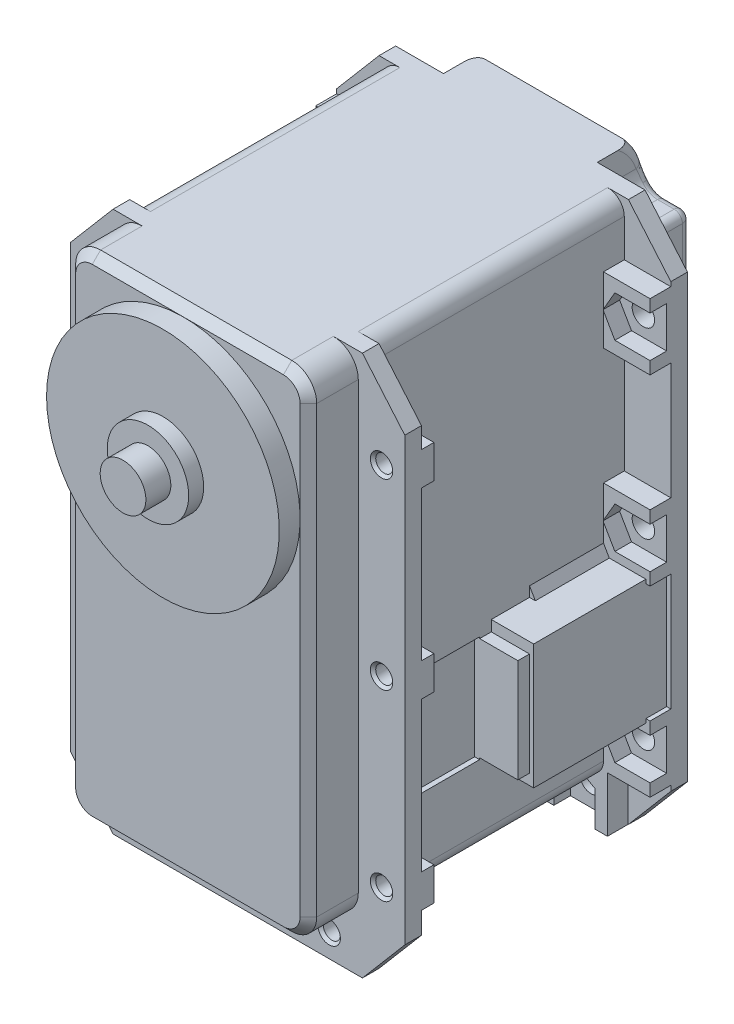
SolidWorks part; units mm, degrees
material "Custom Plastic"
ref_plane "Front Plane" through (0, 0, 0) normal (0, 0, 1) x (1, 0, 0)
ref_plane "Top Plane" through (0, 0, 0) normal (0, 1, 0) x (1, 0, 0)
ref_plane "Right Plane" through (0, 0, 0) normal (1, 0, 0) x (0, 0, -1)
ref_plane "Plane1" through (9.25, 0, 0) normal (1, 0, 0) x (0, 0, -1)
sketch "Sketch1" plane through (9.25, 0, 0) normal (1, 0, 0) x (0, 0, -1)
  line L0 (21, 14.5) -> (21, 9.5)
  line L1 (21, 9.5) -> (23, 9.5)
  arc A0 (23, 9.5) -> (21, 14.5) centre (15.75, 9.5) ccw
extrude "Boss-Extrude1" add sketch "Sketch1" against normal blind 18.5
ref_plane "Plane2" through (0, 9.5, 0) normal (0, -1, 0) x (1, 0, 0)
sketch "Sketch2" plane through (0, 9.5, 0) normal (0, -1, 0) x (1, 0, 0)
  line L0 (-15.8711, -21) -> (-15.8711, -23)
  line L1 (-15.8711, -23) -> (-9.25, -23)
  line L2 (-9.25, -23) -> (-9.25, -21)
  line L3 (-9.25, -21) -> (-15.8711, -21)
extrude "Boss-Extrude2" add sketch "Sketch2" against normal blind 5
sketch "Sketch3" plane through (0, 9.5, 0) normal (0, -1, 0) x (1, 0, 0)
  line L0 (9.25, -21) -> (9.25, -23)
  line L1 (9.25, -23) -> (20.1, -23)
  line L2 (20.1, -23) -> (20.1, -21)
  line L3 (20.1, -21) -> (9.25, -21)
extrude "Boss-Extrude3" add sketch "Sketch3" against normal blind 5
sketch "Sketch4" plane through (0, 9.5, 0) normal (0, -1, 0) x (1, 0, 0)
  line L0 (20.1, -21) -> (20.1, -23)
  line L1 (20.1, -23) -> (-15.8711, -23)
  line L2 (-15.8711, -23) -> (-15.8711, -21)
  line L3 (-15.8711, -21) -> (20.1, -21)
extrude "Boss-Extrude4" add sketch "Sketch4" along normal blind 60.1
sketch "Sketch5" plane through (0, 0, -21) normal (0, 0, 1) x (1, 0, 0)
  line L0 (-15.8711, -50.6) -> (-15.8711, 14.5)
  line L1 (-15.8711, 14.5) -> (20.1, 14.5)
  line L2 (20.1, 14.5) -> (20.1, -50.6)
  line L3 (20.1, -50.6) -> (-15.8711, -50.6)
extrude "Boss-Extrude5" add sketch "Sketch5" along normal blind 6.5
sketch "Sketch6" plane through (0, 0, -23) normal (0, 0, -1) x (-1, 0, 0)
  line L0 (15.8711, -50.6) -> (15.8711, 14.5)
  line L1 (15.8711, 14.5) -> (9.25, 14.5)
  line L2 (9.25, 14.5) -> (9.25, -45)
  line L3 (9.25, -45) -> (-9.25, -45)
  line L4 (-9.25, -45) -> (-9.25, 14.5)
  line L5 (-9.25, 14.5) -> (-20.1, 14.5)
  line L6 (-20.1, 14.5) -> (-20.1, -50.6)
  line L7 (-20.1, -50.6) -> (15.8711, -50.6)
extrude "Cut-Extrude1" cut sketch "Sketch6" against normal blind 2
sketch "Sketch7" plane through (0, 0, -14.5) normal (0, 0, 1) x (1, 0, 0)
  line L0 (-15.8711, -20.475) -> (-14.5, -18.1003)
  line L1 (-14.5, -18.1003) -> (-14.5, -17.8997)
  line L2 (-14.5, -17.8997) -> (-15.8711, -15.525)
  line L3 (-15.8711, -15.525) -> (-15.8711, 1.525)
  line L4 (-15.8711, 1.525) -> (-14.5, 3.8997)
  line L5 (-14.5, 3.8997) -> (-14.5, 4.1003)
  line L6 (-14.5, 4.1003) -> (-15.8711, 6.475)
  line L7 (-15.8711, 6.475) -> (-15.8711, 14.5)
  line L8 (-15.8711, 14.5) -> (20.1, 14.5)
  line L9 (20.1, 14.5) -> (20.1, -50.6)
  line L10 (20.1, -50.6) -> (-15.8711, -50.6)
  line L11 (-15.8711, -50.6) -> (-15.8711, -42.475)
  line L12 (-15.8711, -42.475) -> (-14.5, -40.1003)
  line L13 (-14.5, -40.1003) -> (-14.5, -39.8997)
  line L14 (-14.5, -39.8997) -> (-15.8711, -37.525)
  line L15 (-15.8711, -37.525) -> (-15.8711, -20.475)
extrude "Boss-Extrude6" add sketch "Sketch7" along normal blind 2
sketch "Sketch8" plane through (0, 0, -21) normal (0, 0, -1) x (-1, 0, 0)
  line L0 (15.8711, -50.6) -> (15.8711, 14.5)
  line L1 (15.8711, 14.5) -> (9.25, 14.5)
  line L2 (9.25, 14.5) -> (9.25, -45)
  line L3 (9.25, -45) -> (-9.25, -45)
  line L4 (-9.25, -45) -> (-9.25, 14.5)
  line L5 (-9.25, 14.5) -> (-20.1, 14.5)
  line L6 (-20.1, 14.5) -> (-20.1, -50.6)
  line L7 (-20.1, -50.6) -> (15.8711, -50.6)
extrude "Cut-Extrude2" cut sketch "Sketch8" against normal blind 4
sketch "Sketch9" plane through (0, 0, -12.5) normal (0, 0, 1) x (1, 0, 0)
  line L0 (20.1, 14.5) -> (20.1, -50.6)
  line L1 (20.1, -50.6) -> (-15.8711, -50.6)
  line L2 (-15.8711, -50.6) -> (-15.8711, -42.475)
  line L3 (-15.8711, -42.475) -> (-14.5, -40.1003)
  line L4 (-14.5, -40.1003) -> (-14.5, 14.5)
  line L5 (-14.5, 14.5) -> (20.1, 14.5)
extrude "Boss-Extrude7" add sketch "Sketch9" along normal blind 29.5
sketch "Sketch10" plane through (0, 0, 17) normal (0, 0, 1) x (1, 0, 0)
  line L0 (14.5, 14.5) -> (14.5, -45)
  line L1 (14.5, -45) -> (-14.5, -45)
  line L2 (-14.5, -45) -> (-14.5, -40.1003)
  line L3 (-14.5, -40.1003) -> (-15.8711, -42.475)
  line L4 (-15.8711, -42.475) -> (-15.8711, -50.6)
  line L5 (-15.8711, -50.6) -> (20.1, -50.6)
  line L6 (20.1, -50.6) -> (20.1, 14.5)
  line L7 (20.1, 14.5) -> (14.5, 14.5)
extrude "Cut-Extrude3" cut sketch "Sketch10" against normal blind 29.5
sketch "Sketch11" plane through (0, 0, -12.5) normal (0, 0, 1) x (1, 0, 0)
  line L0 (-13.475, -46.3711) -> (-13.475, -50.6)
  line L1 (-13.475, -50.6) -> (-8.525, -50.6)
  line L2 (-8.525, -50.6) -> (-8.525, -46.3711)
  line L3 (-8.525, -46.3711) -> (-11, -44.9421)
  line L4 (-11, -44.9421) -> (-13.475, -46.3711)
extrude "Cut-Extrude4" cut sketch "Sketch11" against normal blind 2
sketch "Sketch12" plane through (0, 0, -12.5) normal (0, 0, 1) x (1, 0, 0)
  line L0 (8.525, -46.3711) -> (8.525, -50.6)
  line L1 (8.525, -50.6) -> (13.475, -50.6)
  line L2 (13.475, -50.6) -> (13.475, -46.3711)
  line L3 (13.475, -46.3711) -> (11, -44.9421)
  line L4 (11, -44.9421) -> (8.525, -46.3711)
extrude "Cut-Extrude5" cut sketch "Sketch12" against normal blind 2
sketch "Sketch13" plane through (0, 0, -12.5) normal (0, 0, 1) x (1, 0, 0)
  line L0 (15.8711, -42.475) -> (20.1, -42.475)
  line L1 (20.1, -42.475) -> (20.1, -37.525)
  line L2 (20.1, -37.525) -> (15.8711, -37.525)
  line L3 (15.8711, -37.525) -> (14.4421, -40)
  line L4 (14.4421, -40) -> (15.8711, -42.475)
extrude "Cut-Extrude6" cut sketch "Sketch13" against normal blind 2
sketch3d "3DSketch1"
  point P0 (0.3206, -15.6432, -2.4982)
  point P1 (0.3206, 84.3568, -2.4982)
ref_axis "Axis1" through (0.3206, -15.6432, -2.4982) along (0, 1, 0)
pattern_linear "LPattern1" count 3 spacing 22 along (0, 1, 0) of "Cut-Extrude6"
ref_plane "Plane3" through (0, 0, -14.5) normal (0, 0, -1) x (-1, 0, 0)
sketch "Sketch14" plane through (0, 0, -14.5) normal (0, 0, -1) x (-1, 0, 0)
  line L0 (14.4421, -40) -> (14.5, -40.1003)
  line L1 (14.5, -40.1003) -> (14.5, -39.8997)
  line L2 (14.5, -39.8997) -> (14.4421, -40)
extrude "Cut-Extrude7" cut sketch "Sketch14" against normal blind 2
sketch3d "3DSketch2"
  point P0 (0.2957, -15.6557, -2.4823)
  point P1 (0.2957, 84.3443, -2.4823)
ref_axis "Axis2" through (0.2957, -15.6557, -2.4823) along (0, 1, 0)
pattern_linear "LPattern2" count 3 spacing 22 along (0, 1, 0) of "Cut-Extrude7"
sketch "Sketch15" plane through (-15.8711, 0, 0) normal (-1, 0, 0) x (0, 0, 1)
  line L0 (-12.5, 14.5) -> (-12.5, 6.475)
  line L1 (-12.5, 6.475) -> (-14.5, 6.475)
  line L2 (-14.5, 6.475) -> (-14.5, 1.525)
  line L3 (-14.5, 1.525) -> (-12.5, 1.525)
  line L4 (-12.5, 1.525) -> (-12.5, -15.525)
  line L5 (-12.5, -15.525) -> (-14.5, -15.525)
  line L6 (-14.5, -15.525) -> (-14.5, -20.475)
  line L7 (-14.5, -20.475) -> (-12.5, -20.475)
  line L8 (-12.5, -20.475) -> (-12.5, -37.525)
  line L9 (-12.5, -37.525) -> (-14.5, -37.525)
  line L10 (-14.5, -37.525) -> (-14.5, -42.475)
  line L11 (-14.5, -42.475) -> (-12.5, -42.475)
  line L12 (-12.5, -42.475) -> (-12.5, -50.6)
  line L13 (-12.5, -50.6) -> (-17, -50.6)
  line L14 (-17, -50.6) -> (-17, 14.5)
  line L15 (-17, 14.5) -> (-12.5, 14.5)
extrude "Boss-Extrude8" add sketch "Sketch15" along normal blind 4.2289
sketch "Sketch16" plane through (-14.5, 0, 0) normal (-1, 0, 0) x (0, 0, 1)
  line L0 (15, -45) -> (15, 14.5)
  line L1 (15, 14.5) -> (17, 14.5)
  line L2 (17, 14.5) -> (17, -45)
  line L3 (17, -45) -> (15, -45)
extrude "Boss-Extrude9" add sketch "Sketch16" along normal blind 5.6
sketch "Sketch17" plane through (0, -45, 0) normal (0, -1, 0) x (1, 0, 0)
  line L0 (14.5, 15) -> (-20.1, 15)
  line L1 (-20.1, 15) -> (-20.1, 17)
  line L2 (-20.1, 17) -> (14.5, 17)
  line L3 (14.5, 17) -> (14.5, 15)
extrude "Boss-Extrude10" add sketch "Sketch17" along normal blind 5.6
sketch "Sketch18" plane through (14.5, 0, 0) normal (1, 0, 0) x (0, 0, -1)
  line L0 (-15, -50.6) -> (-17, -50.6)
  line L1 (-17, -50.6) -> (-17, 14.5)
  line L2 (-17, 14.5) -> (-15, 14.5)
  line L3 (-15, 14.5) -> (-15, -50.6)
extrude "Boss-Extrude11" add sketch "Sketch18" along normal blind 5.6
sketch "Sketch19" plane through (14.5, 0, 0) normal (1, 0, 0) x (0, 0, -1)
  line L0 (-1, -21.5) -> (12.5, -21.5)
  line L1 (12.5, -21.5) -> (12.5, -36.5)
  line L2 (12.5, -36.5) -> (-1, -36.5)
  line L3 (-1, -36.5) -> (-1, -21.5)
extrude "Boss-Extrude12" add sketch "Sketch19" along normal blind 5.1
sketch "Sketch20" plane through (0, 0, 1) normal (0, 0, 1) x (1, 0, 0)
  line L0 (19.1, -35.21) -> (14.5, -35.21)
  line L1 (14.5, -35.21) -> (14.5, -22.79)
  line L2 (14.5, -22.79) -> (19.1, -22.79)
  line L3 (19.1, -22.79) -> (19.1, -35.21)
extrude "Boss-Extrude13" add sketch "Sketch20" along normal blind 1.4
sketch "Sketch21" plane through (14.5, 0, 0) normal (1, 0, 0) x (0, 0, -1)
  line L0 (-2.4, -35.4) -> (-2.4, -22.6)
  line L1 (-2.4, -22.6) -> (-12.5, -22.6)
  line L2 (-12.5, -22.6) -> (-12.5, -35.4)
  line L3 (-12.5, -35.4) -> (-2.4, -35.4)
extrude "Cut-Extrude8" cut sketch "Sketch21" against normal blind 0.6
sketch "Sketch22" plane through (-14.5, 0, 0) normal (-1, 0, 0) x (0, 0, 1)
  line L0 (1, -36.5) -> (-12.5, -36.5)
  line L1 (-12.5, -36.5) -> (-12.5, -21.5)
  line L2 (-12.5, -21.5) -> (1, -21.5)
  line L3 (1, -21.5) -> (1, -36.5)
extrude "Boss-Extrude14" add sketch "Sketch22" along normal blind 5.1
sketch "Sketch23" plane through (0, 0, 1) normal (0, 0, 1) x (1, 0, 0)
  line L0 (-19.1, -22.79) -> (-14.5, -22.79)
  line L1 (-14.5, -22.79) -> (-14.5, -35.21)
  line L2 (-14.5, -35.21) -> (-19.1, -35.21)
  line L3 (-19.1, -35.21) -> (-19.1, -22.79)
extrude "Boss-Extrude15" add sketch "Sketch23" along normal blind 1.4
sketch "Sketch24" plane through (-14.5, 0, 0) normal (-1, 0, 0) x (0, 0, 1)
  line L0 (2.4, -22.6) -> (2.4, -35.4)
  line L1 (2.4, -35.4) -> (12.5, -35.4)
  line L2 (12.5, -35.4) -> (12.5, -22.6)
  line L3 (12.5, -22.6) -> (2.4, -22.6)
extrude "Cut-Extrude9" cut sketch "Sketch24" against normal blind 0.6
sketch "Sketch25" plane through (0, -50.6, 0) normal (0, -1, 0) x (1, 0, 0)
  line L0 (7.025, -15) -> (7.025, -12.5)
  line L1 (7.025, -12.5) -> (-7.025, -12.5)
  line L2 (-7.025, -12.5) -> (-7.025, -15)
  line L3 (-7.025, -15) -> (7.025, -15)
extrude "Cut-Extrude10" cut sketch "Sketch25" against normal blind 5.6
sketch "Sketch26" plane through (20.1, 0, 0) normal (1, 0, 0) x (0, 0, -1)
  line L0 (15, -21.975) -> (12.5, -21.975)
  line L1 (12.5, -21.975) -> (12.5, -36.025)
  line L2 (12.5, -36.025) -> (15, -36.025)
  line L3 (15, -36.025) -> (15, -21.975)
extrude "Cut-Extrude11" cut sketch "Sketch26" against normal blind 0.5
sketch "Sketch27" plane through (20.1, 0, 0) normal (1, 0, 0) x (0, 0, -1)
  line L0 (15, 0.025) -> (12.5, 0.025)
  line L1 (12.5, 0.025) -> (12.5, -14.025)
  line L2 (12.5, -14.025) -> (15, -14.025)
  line L3 (15, -14.025) -> (15, 0.025)
extrude "Cut-Extrude12" cut sketch "Sketch27" against normal blind 5.6
sketch "Sketch28" plane through (20.1, 0, 0) normal (1, 0, 0) x (0, 0, -1)
  line L0 (12.5, 7.975) -> (15, 7.975)
  line L1 (15, 7.975) -> (15, 14.5)
  line L2 (15, 14.5) -> (12.5, 14.5)
  line L3 (12.5, 14.5) -> (12.5, 7.975)
extrude "Cut-Extrude13" cut sketch "Sketch28" against normal blind 5.6
sketch "Sketch29" plane through (-20.1, 0, 0) normal (-1, 0, 0) x (0, 0, 1)
  line L0 (-15, 7.975) -> (-12.5, 7.975)
  line L1 (-12.5, 7.975) -> (-12.5, 14.5)
  line L2 (-12.5, 14.5) -> (-15, 14.5)
  line L3 (-15, 14.5) -> (-15, 7.975)
extrude "Cut-Extrude14" cut sketch "Sketch29" against normal blind 5.6
sketch "Sketch30" plane through (-20.1, 0, 0) normal (-1, 0, 0) x (0, 0, 1)
  line L0 (-12.5, 0.025) -> (-15, 0.025)
  line L1 (-15, 0.025) -> (-15, -14.025)
  line L2 (-15, -14.025) -> (-12.5, -14.025)
  line L3 (-12.5, -14.025) -> (-12.5, 0.025)
extrude "Cut-Extrude15" cut sketch "Sketch30" against normal blind 5.6
sketch "Sketch31" plane through (-20.1, 0, 0) normal (-1, 0, 0) x (0, 0, 1)
  line L0 (-15, -36.025) -> (-12.5, -36.025)
  line L1 (-12.5, -36.025) -> (-12.5, -21.975)
  line L2 (-12.5, -21.975) -> (-15, -21.975)
  line L3 (-15, -21.975) -> (-15, -36.025)
extrude "Cut-Extrude16" cut sketch "Sketch31" against normal blind 0.5
sketch "Sketch32" plane through (0, -45, 0) normal (0, -1, 0) x (1, 0, 0)
  line L0 (-13, 13.5) -> (-13, 15)
  line L1 (-13, 15) -> (-9, 15)
  line L2 (-9, 15) -> (-9, 13.5)
  line L3 (-9, 13.5) -> (-13, 13.5)
extrude "Boss-Extrude16" add sketch "Sketch32" along normal blind 5.6
sketch "Sketch33" plane through (0, -45, 0) normal (0, -1, 0) x (1, 0, 0)
  line L0 (9, 13.5) -> (9, 15)
  line L1 (9, 15) -> (13, 15)
  line L2 (13, 15) -> (13, 13.5)
  line L3 (13, 13.5) -> (9, 13.5)
extrude "Boss-Extrude17" add sketch "Sketch33" along normal blind 5.6
sketch "Sketch34" plane through (14.5, 0, 0) normal (1, 0, 0) x (0, 0, -1)
  line L0 (-13.5, 2) -> (-15, 2)
  line L1 (-15, 2) -> (-15, 6)
  line L2 (-15, 6) -> (-13.5, 6)
  line L3 (-13.5, 6) -> (-13.5, 2)
extrude "Boss-Extrude18" add sketch "Sketch34" along normal blind 5.6
sketch3d "3DSketch3"
  point P0 (0.0081, -16.3123, -2.1724)
  point P1 (0.0081, -116.3123, -2.1724)
ref_axis "Axis3" through (0.0081, -16.3123, -2.1724) along (0, -1, 0)
pattern_linear "LPattern3" count 3 spacing 22 along (0, -1, 0) of "Boss-Extrude18"
sketch "Sketch35" plane through (-14.5, 0, 0) normal (-1, 0, 0) x (0, 0, 1)
  line L0 (15, 2) -> (13.5, 2)
  line L1 (13.5, 2) -> (13.5, 6)
  line L2 (13.5, 6) -> (15, 6)
  line L3 (15, 6) -> (15, 2)
extrude "Boss-Extrude19" add sketch "Sketch35" along normal blind 5.6
pattern_linear "LPattern4" count 3 spacing 22 along (0, -1, 0) of "Boss-Extrude19"
sketch "Sketch36" plane through (0, 0, -17) normal (0, 0, -1) x (-1, 0, 0)
  line L0 (-14.5, 9.25) -> (-9.25, 9.25)
  line L1 (-9.25, 9.25) -> (-9.25, -39.75)
  line L2 (-9.25, -39.75) -> (-14.5, -39.75)
  line L3 (-14.5, -39.75) -> (-14.5, 9.25)
extrude "Boss-Extrude20" add sketch "Sketch36" along normal blind 6
sketch "Sketch37" plane through (0, 0, -17) normal (0, 0, -1) x (-1, 0, 0)
  line L0 (14.5, -39.75) -> (9.25, -39.75)
  line L1 (9.25, -39.75) -> (9.25, 9.25)
  line L2 (9.25, 9.25) -> (14.5, 9.25)
  line L3 (14.5, 9.25) -> (14.5, -39.75)
extrude "Boss-Extrude21" add sketch "Sketch37" along normal blind 6
sketch "Sketch38" plane through (0, 0, -12.5) normal (0, 0, 1) x (1, 0, 0)
  line L0 (15.2, -21.5) -> (14.5, -21.5)
  line L1 (14.5, -21.5) -> (14.5, -20.2876)
  line L2 (14.5, -20.2876) -> (15.2, -21.5)
extrude "Boss-Extrude22" add sketch "Sketch38" along normal blind 8.9
sketch "Sketch39" plane through (0, 0, -12.5) normal (0, 0, 1) x (1, 0, 0)
  line L0 (14.975, -43.975) -> (14.975, -50.6)
  line L1 (14.975, -50.6) -> (20.1, -50.6)
  line L2 (20.1, -50.6) -> (20.1, -43.975)
  line L3 (20.1, -43.975) -> (14.975, -43.975)
extrude "Cut-Extrude17" cut sketch "Sketch39" against normal blind 2.5
sketch "Sketch40" plane through (0, -50.6, 0) normal (0, -1, 0) x (1, 0, 0)
  line L0 (-20.1, -15) -> (-14.975, -15)
  line L1 (-14.975, -15) -> (-14.975, -12.5)
  line L2 (-14.975, -12.5) -> (-20.1, -12.5)
  line L3 (-20.1, -12.5) -> (-20.1, -15)
extrude "Cut-Extrude18" cut sketch "Sketch40" against normal blind 6.625
sketch "Sketch41" plane through (0, 0, 17) normal (0, 0, 1) x (1, 0, 0)
  line L0 (-14.5, -45) -> (-14.5, 14.5)
  line L1 (-14.5, 14.5) -> (14.5, 14.5)
  line L2 (14.5, 14.5) -> (14.5, -45)
  line L3 (14.5, -45) -> (-14.5, -45)
extrude "Boss-Extrude23" add sketch "Sketch41" along normal blind 6
sketch "Sketch42" plane through (0, 0, -12.5) normal (0, 0, 1) x (1, 0, 0)
  line L0 (-15.2, -21.5) -> (-14.5, -20.2876)
  line L1 (-14.5, -20.2876) -> (-14.5, -21.5)
  line L2 (-14.5, -21.5) -> (-15.2, -21.5)
extrude "Boss-Extrude24" add sketch "Sketch42" along normal blind 8.9
sketch "Sketch43" plane through (-14.5, 0, 0) normal (-1, 0, 0) x (0, 0, 1)
  line L0 (-8.8, -13.45) -> (-5, -13.45)
  line L1 (-5, -13.45) -> (-5, -7.55)
  line L2 (-5, -7.55) -> (-8.8, -7.55)
  line L3 (-8.8, -7.55) -> (-8.8, -13.45)
extrude "Cut-Extrude19" cut sketch "Sketch43" against normal blind 1
hole_wizard "Hole1" positions "Sketch45" profile "Sketch44" legacy
sketch "Sketch45" plane through (0, 0, -23) normal (0, 0, -1) x (-1, 0, 0)
  point P0 (0, 0)
sketch "Sketch44" plane through (0, 0, -23) normal (1, 0, 0) x (0, 1, 0)
  line L0 (0, 0) -> (0, 1)
  line L1 (0, 1) -> (7.5, 1)
  line L2 (7.5, 1) -> (7.5, 0)
  line L3 (7.5, 0) -> (0, 0)
  line L4 (0, 110) -> (0, -10) construction
  dimension "Diameter" = 15
  dimension "Depth" = 1
ref_plane "Plane4" through (0, 0, 0) normal (0, -1, 0) x (1, 0, 0)
sketch "Sketch46" plane through (0, 0, 0) normal (0, -1, 0) x (1, 0, 0)
  line L0 (2.75, 30.8) -> (0, 30.8)
  line L1 (0, 30.8) -> (0, 23)
  line L2 (0, 23) -> (5, 23)
  line L3 (5, 23) -> (5, 23.5)
  line L4 (5, 23.5) -> (14, 23.5)
  line L5 (14, 23.5) -> (14, 26)
  line L6 (14, 26) -> (5, 26)
  line L7 (5, 26) -> (5, 27.8)
  line L8 (5, 27.8) -> (2.75, 27.8)
  line L9 (2.75, 27.8) -> (2.75, 30.8)
  line L10 (0, 30.8) -> (0, 23) construction
revolve "Revolve1" add sketch "Sketch46" angle 360 about L10 reverse direction yes
sketch "Sketch47" plane through (0, 0, 0) normal (0, -1, 0) x (1, 0, 0)
  line L0 (5, -22) -> (0, -22)
  line L1 (0, -22) -> (0, -24.5)
  line L2 (0, -24.5) -> (4, -24.5)
  line L3 (4, -24.5) -> (4, -22.3)
  line L4 (4, -22.3) -> (5, -22.3)
  line L5 (5, -22.3) -> (5, -22)
  line L6 (0, -22) -> (0, -24.5) construction
revolve "Revolve2" add sketch "Sketch47" angle 360 about L6 reverse direction yes
hole_wizard "Hole2" positions "Sketch49" profile "Sketch48" legacy
sketch "Sketch49" plane through (0, 0, -14.5) normal (0, 0, 1) x (1, 0, 0)
  point P0 (17.3, -40)
sketch "Sketch48" plane through (17.3, -40, -14.5) normal (1, 0, 0) x (0, -1, 0)
  line L0 (0, 0) -> (0, 10)
  line L1 (0, 10) -> (1.35, 10)
  line L2 (1.35, 10) -> (1.35, 0)
  line L3 (1.35, 0) -> (0, 0)
  line L4 (0, 110) -> (0, -10) construction
  dimension "Diameter" = 2.7
  dimension "Depth" = 10
sketch3d "3DSketch4"
  point P0 (0.0008, -15.7705, 0.4564)
  point P1 (0.0008, 84.2295, 0.4564)
ref_axis "Axis4" through (0.0008, -15.7705, 0.4564) along (0, 1, 0)
pattern_linear "LPattern5" count 3 spacing 22 along (0, 1, 0) of "Hole2"
hole_wizard "Hole3" positions "Sketch51" profile "Sketch50" legacy
sketch "Sketch51" plane through (0, 0, -14.5) normal (0, 0, 1) x (1, 0, 0)
  point P0 (-17.3, -40)
sketch "Sketch50" plane through (-17.3, -40, -14.5) normal (1, 0, 0) x (0, -1, 0)
  line L0 (0, 0) -> (0, 10)
  line L1 (0, 10) -> (1.35, 10)
  line L2 (1.35, 10) -> (1.35, 0)
  line L3 (1.35, 0) -> (0, 0)
  line L4 (0, 110) -> (0, -10) construction
  dimension "Diameter" = 2.7
  dimension "Depth" = 10
sketch3d "3DSketch5"
  point P0 (-0.0021, -15.7694, 0.4644)
  point P1 (-0.0021, 84.2306, 0.4644)
ref_axis "Axis5" through (-0.0021, -15.7694, 0.4644) along (0, 1, 0)
pattern_linear "LPattern6" count 3 spacing 22 along (0, 1, 0) of "Hole3"
hole_wizard "Hole4" positions "Sketch53" profile "Sketch52" legacy
sketch "Sketch53" plane through (0, 0, -14.5) normal (0, 0, 1) x (1, 0, 0)
  point P0 (11, -47.8)
sketch "Sketch52" plane through (11, -47.8, -14.5) normal (1, 0, 0) x (0, -1, 0)
  line L0 (0, 0) -> (0, 10)
  line L1 (0, 10) -> (1.35, 10)
  line L2 (1.35, 10) -> (1.35, 0)
  line L3 (1.35, 0) -> (0, 0)
  line L4 (0, 110) -> (0, -10) construction
  dimension "Diameter" = 2.7
  dimension "Depth" = 10
hole_wizard "Hole5" positions "Sketch55" profile "Sketch54" legacy
sketch "Sketch55" plane through (0, 0, -14.5) normal (0, 0, 1) x (1, 0, 0)
  point P0 (-11, -47.8)
sketch "Sketch54" plane through (-11, -47.8, -14.5) normal (1, 0, 0) x (0, -1, 0)
  line L0 (0, 0) -> (0, 10)
  line L1 (0, 10) -> (1.35, 10)
  line L2 (1.35, 10) -> (1.35, 0)
  line L3 (1.35, 0) -> (0, 0)
  line L4 (0, 110) -> (0, -10) construction
  dimension "Diameter" = 2.7
  dimension "Depth" = 10
hole_wizard "Hole6" positions "Sketch57" profile "Sketch56" legacy
sketch "Sketch57" plane through (0, 0, 17) normal (0, 0, 1) x (1, 0, 0)
  point P0 (-11, -47.8)
sketch "Sketch56" plane through (-11, -47.8, 17) normal (1, 0, 0) x (0, -1, 0)
  line L0 (0, 0) -> (0, 41.5)
  line L1 (0, 41.5) -> (1.025, 41.5)
  line L2 (1.025, 41.5) -> (1.025, 0)
  line L3 (1.025, 0) -> (0, 0)
  line L4 (0, 110) -> (0, -10) construction
  dimension "Diameter" = 2.05
  dimension "Depth" = 41.5
hole_wizard "Hole7" positions "Sketch59" profile "Sketch58" legacy
sketch "Sketch59" plane through (0, 0, 17) normal (0, 0, 1) x (1, 0, 0)
  point P0 (-17.3, 4)
sketch "Sketch58" plane through (-17.3, 4, 17) normal (1, 0, 0) x (0, -1, 0)
  line L0 (0, 0) -> (0, 41.5)
  line L1 (0, 41.5) -> (1.025, 41.5)
  line L2 (1.025, 41.5) -> (1.025, 0)
  line L3 (1.025, 0) -> (0, 0)
  line L4 (0, 110) -> (0, -10) construction
  dimension "Diameter" = 2.05
  dimension "Depth" = 41.5
sketch3d "3DSketch6"
  point P0 (0.0074, -15.7601, 0.4711)
  point P1 (0.0074, -115.7601, 0.4711)
ref_axis "Axis6" through (0.0074, -15.7601, 0.4711) along (0, -1, 0)
pattern_linear "LPattern7" count 3 spacing 22 along (0, -1, 0) of "Hole7"
hole_wizard "Hole8" positions "Sketch61" profile "Sketch60" legacy
sketch "Sketch61" plane through (0, 0, 17) normal (0, 0, 1) x (1, 0, 0)
  point P0 (11, -47.8)
sketch "Sketch60" plane through (11, -47.8, 17) normal (1, 0, 0) x (0, -1, 0)
  line L0 (0, 0) -> (0, 41.5)
  line L1 (0, 41.5) -> (1.025, 41.5)
  line L2 (1.025, 41.5) -> (1.025, 0)
  line L3 (1.025, 0) -> (0, 0)
  line L4 (0, 110) -> (0, -10) construction
  dimension "Diameter" = 2.05
  dimension "Depth" = 41.5
hole_wizard "Hole9" positions "Sketch63" profile "Sketch62" legacy
sketch "Sketch63" plane through (0, 0, 17) normal (0, 0, 1) x (1, 0, 0)
  point P0 (17.3, -40)
sketch "Sketch62" plane through (17.3, -40, 17) normal (1, 0, 0) x (0, -1, 0)
  line L0 (0, 0) -> (0, 41.5)
  line L1 (0, 41.5) -> (1.025, 41.5)
  line L2 (1.025, 41.5) -> (1.025, 0)
  line L3 (1.025, 0) -> (0, 0)
  line L4 (0, 110) -> (0, -10) construction
  dimension "Diameter" = 2.05
  dimension "Depth" = 41.5
sketch3d "3DSketch7"
  point P0 (0.0082, -15.7491, 0.4633)
  point P1 (0.0082, 84.2509, 0.4633)
ref_axis "Axis7" through (0.0082, -15.7491, 0.4633) along (0, 1, 0)
pattern_linear "LPattern8" count 3 spacing 22 along (0, 1, 0) of "Hole9"
hole_wizard "Hole10" positions "Sketch65" profile "Sketch64" legacy
sketch "Sketch65" plane through (0, 0, -24.5) normal (0, 0, -1) x (-1, 0, 0)
  point P0 (0, 0)
sketch "Sketch64" plane through (0, 0, -24.5) normal (1, 0, 0) x (0, 1, 0)
  line L0 (0, 0) -> (0, 2.2)
  line L1 (0, 2.2) -> (1.6, 2.2)
  line L2 (1.6, 2.2) -> (1.6, 0)
  line L3 (1.6, 0) -> (0, 0)
  line L4 (0, 110) -> (0, -10) construction
  dimension "Diameter" = 3.2
  dimension "Depth" = 2.2
fillet "Fillet1" radius 2 1 edges at (-14.5, -45, 1.25) tangent propagation no
fillet "Fillet2" radius 2 1 edges at (14.5, -45, 1.25) tangent propagation no
fillet "Fillet3" radius 2.25 1 edges at (-9.25, 9.25, -20) tangent propagation no
fillet "Fillet4" radius 2.25 1 edges at (9.25, 9.25, -20) tangent propagation no
fillet "Fillet5" radius 2.25 1 edges at (9.25, -39.75, -20) tangent propagation no
fillet "Fillet6" radius 2.25 1 edges at (-9.25, -39.75, -20) tangent propagation no
fillet "Fillet7" radius 3 1 edges at (-14.5, -45, 20) tangent propagation no
fillet "Fillet8" radius 3 1 edges tangent propagation no
fillet "Fillet9" radius 3 1 edges tangent propagation no
fillet "Fillet10" radius 3 1 edges at (14.5, -45, 20) tangent propagation no
chamfer "Chamfer1" distance 0.325 angle 45 1 edges at (18.325, -18, 17)
chamfer "Chamfer2" distance 5.1 angle 49.635 1 edges at (-20.1, -50.6, -16) first distance on face at (0, -50.6, -14.1)
chamfer "Chamfer3" distance 5.1 angle 49.635 1 edges at (-20.1, 14.5, 16) first distance on face at (-0.0325, 14.5, 1.15)
chamfer "Chamfer4" distance 5.1 angle 49.635 1 edges at (20.1, -50.6, 16) first distance on face at (0, -50.6, 14.8333)
chamfer "Chamfer5" distance 6 angle 40.365 1 edges at (-20.1, 14.5, -16) first distance on face at (-20.1, -17.5786, -13.9643)
chamfer "Chamfer6" distance 6 angle 40.365 1 edges at (20.1, -50.6, -16) first distance on face at (20.1, -18.0071, -13.9643)
chamfer "Chamfer7" distance 5.1 angle 49.635 1 edges at (20.1, 14.5, -16) first distance on face at (0.86, 14.5, 1.15)
chamfer "Chamfer8" distance 6 angle 40.365 1 edges at (20.1, 14.5, 16) first distance on face at (20.1, -17.2625, 14.6875)
chamfer "Chamfer9" distance 0.325 angle 45 1 edges at (-9.975, -47.8, 17)
chamfer "Chamfer10" distance 0.325 angle 45 1 edges at (-16.275, -40, 17)
chamfer "Chamfer11" distance 0.325 angle 45 1 edges at (-16.275, -18, 17)
chamfer "Chamfer12" distance 6 angle 40.365 1 edges at (-20.1, -50.6, 16) first distance on face at (-20.1, -18.7625, 14.6875)
chamfer "Chamfer13" distance 0.325 angle 45 1 edges at (-16.275, 4, 17)
chamfer "Chamfer14" distance 0.325 angle 45 1 edges at (12.025, -47.8, 17)
chamfer "Chamfer15" distance 0.325 angle 45 1 edges at (18.325, -40, 17)
chamfer "Chamfer16" distance 0.325 angle 45 1 edges at (18.325, 4, 17)
chamfer "Chamfer17" distance 1 angle 45 8 edges at (14.5, -15.25, 23) (13.6213, 13.6213, 23) (13.6213, -44.1213, 23) (0, 14.5, 23) (0, -45, 23) (-13.6213, 13.6213, 23) (-13.6213, -44.1213, 23) (-14.5, -15.25, 23)
fillet "Fillet11" radius 1 1 edges at (13, -44.9365, 14.25) tangent propagation no
fillet "Fillet12" radius 1 1 edges at (-13, -44.9365, 14.25) tangent propagation no
fillet "Fillet13" radius 1 1 edges at (-9, -45, 14.25) tangent propagation no
fillet "Fillet14" radius 1 1 edges at (9, -45, 14.25) tangent propagation no
fillet "Fillet15" radius 1 1 edges at (14.5, -38, 14.25) tangent propagation no
fillet "Fillet16" radius 1 1 edges at (14.5, -16, 14.25) tangent propagation no
fillet "Fillet17" radius 1 1 edges at (14.5, 6, 14.25) tangent propagation no
fillet "Fillet18" radius 1 1 edges at (-14.5, -16, 14.25) tangent propagation no
fillet "Fillet19" radius 1 1 edges at (-14.5, -38, 14.25) tangent propagation no
fillet "Fillet20" radius 1 1 edges at (-14.5, 6, 14.25) tangent propagation no
fillet "Fillet21" radius 1 1 edges at (14.5, 2, 14.25) tangent propagation no
fillet "Fillet22" radius 1 1 edges at (-14.5, 2, 14.25) tangent propagation no
fillet "Fillet23" radius 1 1 edges at (14.5, -20, 14.25) tangent propagation no
fillet "Fillet24" radius 1 1 edges at (-14.5, -20, 14.25) tangent propagation no
fillet "Fillet25" radius 1 23 edges at (-13, 9.25, -23) (-10.9697, 9.3134, -23) (-9.455, 10.5616, -22.9219) (-14.5, 9.25, -20) (-14.5, -15.25, -23) (-14.5, -39.75, -20) (-9.909, -40.409, -23) (-13, -39.75, -23) (-9.25, -45, -20) (9.25, -45, -20) (0, -45, -23) (14.5, -39.75, -20) (9.909, -40.409, -23) (13, -39.75, -23) (14.5, -15.25, -23) (14.5, 9.25, -20) (13, 9.25, -23) (10.9697, 9.3134, -23) (9.7149, 10.1304, -22.9725)
fillet "Fillet26" radius 2 1 edges tangent propagation no
fillet "Fillet27" radius 2 1 edges at (14.5, 14.5, 0) tangent propagation no
other "Move Face1" flip direction yes face at (-5, 0, 27.8) offset 0.1 parameters "D1"=0.1
